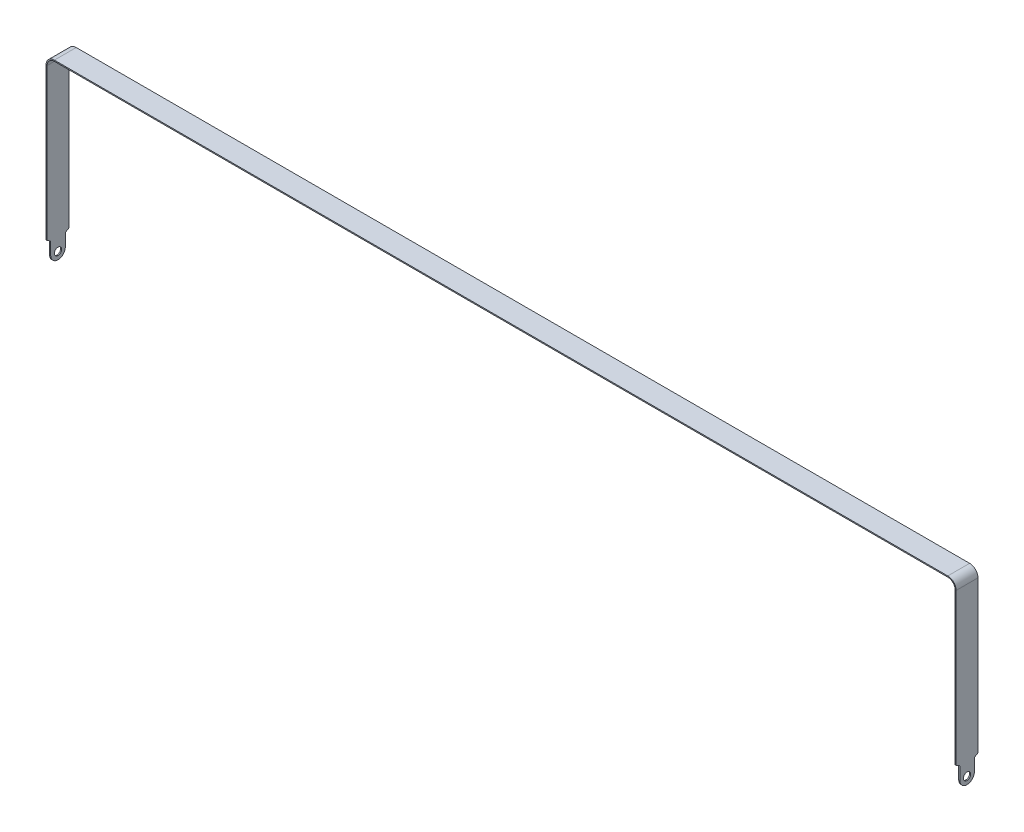
SolidWorks part; units mm, degrees
note: The reader was unsure of these and kept them because the rebuilt part matched: flange length of "Edge-Flange1".
ref_plane "Front Plane" through (0, 0, 0) normal (0, 0, 1) x (1, 0, 0)
ref_plane "Top Plane" through (0, 0, 0) normal (0, 1, 0) x (1, 0, 0)
ref_plane "Right Plane" through (0, 0, 0) normal (1, 0, 0) x (0, 0, -1)
sketch "Sketch1" plane through (0, 0, 0) normal (0, 1, 0) x (1, 0, 0)
  line L3 (-311.75, -7.5) -> (311.75, -7.5)
  line L4 (-311.75, -7.5) -> (-311.75, 7.5)
  line L5 (-311.75, 7.5) -> (311.75, 7.5)
  line L6 (311.75, -7.5) -> (311.75, 7.5)
  line L7 (-311.75, -7.5) -> (311.75, 7.5) construction
  line L8 (-311.75, 7.5) -> (311.75, -7.5) construction
  point P0 (0, 0)
  dimension "D1" = 623.5
  dimension "D2" = 15
base flange "Base-Flange2" sketch "Sketch1" thickness 0.75 reverse thickness direction no parameters "D1"=0.7366
edge flange "Edge-Flange1" sketch "Sketch15" flange profiles "Sketch15", "Sketch16" flange angle 90 flange length 125 flange position material outside bend radius 5 thickness 0.75 relief rectangular parameters "D6"=10, "D8"=0.25
sketch "Sketch15" plane through (311.75, -0.75, 0) normal (-1, 0, 0) x (0, 0, -1)
  line L2 (-7.5, 0) -> (-7.5, 124.25)
  line L3 (-7.5, 124.25) -> (7.5, 124.25)
  line L4 (7.5, 124.25) -> (7.5, 0)
  line L5 (7.5, 0) -> (-7.5, 0) construction
  line L6 (7.5, 0) -> (-7.5, 0)
sketch "Sketch16" plane through (-311.75, -0.75, 0) normal (1, 0, 0) x (0, 0, 1)
  line L0 (7.5, 0) -> (-7.5, 0) construction
  line L1 (7.5, 0) -> (-7.5, 0)
  line L2 (7.5, 0) -> (7.5, 124.25)
  line L3 (7.5, 124.25) -> (-7.5, 124.25)
  line L4 (-7.5, 124.25) -> (-7.5, 0)
bend "EdgeBend1" bend radius 5 bend angle 90 parameters "D5"=1
bend "EdgeBend2" bend radius 5 bend angle 90 parameters "D5"=2
sketch "Sketch17" plane through (312.5, 0, 0) normal (1, 0, 0) x (0, 0, -1)
  line L0 (0, -125) -> (0, -95.6548) construction
  line L1 (7.5, -125) -> (-7.5, -125) construction
  line L4 (-5, -111.2863) -> (-5, -120)
  line L5 (5, -120) -> (5, -111.2863)
  line L6 (5, -111.2863) -> (9.9611, -108.3867)
  line L7 (9.9611, -108.3867) -> (9.9611, -134.1714)
  line L8 (9.9611, -134.1714) -> (-9.9611, -134.1714)
  line L9 (-9.9611, -108.3867) -> (-9.9611, -134.1714)
  line L10 (-5, -111.2863) -> (-9.9611, -108.3867)
  circle A0 centre (0, -120) radius 2.5
  arc A1 (-5, -120) -> (5, -120) centre (0, -120) ccw
  point P14 (0, -134.1714)
  dimension "D2" = 5
  dimension "D1" = 5
  dimension "D3" = 10
extrude "Cut-Extrude1" cut sketch "Sketch17" against normal through all normal cut yes
sketch "Bend-Lines3" [suppressed] plane through (0, 0, 0) normal (0, 1, 0) x (1, 0, 0)
sketch "Bounding-Box3" [suppressed] plane through (0, 0, 0) normal (0, 1, 0) x (1, 0, 0)
sheet metal parameters "Sheet-Metal2" thickness 0.75 parameters "D1"=0.7366
flat pattern "Flat-Pattern2" [suppressed]
sketch "Bend-Lines4" plane through (0, 0, 0) normal (0, 1, 0) x (1, 0, 0)
sketch3d "Bounding-Box4" [suppressed]
  line L0 (-311.75, 6, 0) -> (311.75, 6, 0) construction
  line L1 (-311.75, -6, 0) -> (311.75, -6, 0) construction
  line L2 (-311.75, 6, 0) -> (-311.75, -6, 0) construction
  line L3 (311.75, 6, 0) -> (311.75, -6, 0) construction
sheet metal parameters "Sheet-Metal3" thickness 0.75 parameters "D1"=0.7366
flat pattern "Flat-Pattern2"
sketch "Bend-Lines4" plane through (0, 0, 0) normal (0, 1, 0) x (1, 0, 0)
  line L0 (-310.9715, 6) -> (-310.9715, -6) construction
  line L1 (310.9715, -6) -> (310.9715, 6) construction
  line L2 (-310.9715, 6) -> (-310.9715, -6) construction
  line L3 (310.9715, -6) -> (310.9715, 6) construction
sketch3d "Bounding-Box4" [suppressed]
  line L0 (434.443, 6, 0) -> (-434.443, 6, 0) construction
  line L1 (434.443, -6, 0) -> (-434.443, -6, 0) construction
  line L2 (434.443, 6, 0) -> (434.443, -6, 0) construction
  line L3 (-434.443, 6, 0) -> (-434.443, -6, 0) construction
bend of the flat pattern "Flatten-<EdgeBend1>1"
bend of the flat pattern "Flatten-<EdgeBend2>1"
sheet metal parameters "Sheet-Metal4" thickness 0.75 parameters "D1"=0.7366
flat pattern "Flat-Pattern2"
sketch "Bend-Lines4" plane through (0, 0, 0) normal (0, 1, 0) x (1, 0, 0)
  line L0 (-310.9715, 7.5) -> (-310.9715, -7.5) construction
  line L1 (310.9715, -7.5) -> (310.9715, 7.5) construction
  line L2 (-310.9715, 7.5) -> (-310.9715, -7.5) construction
  line L3 (310.9715, -7.5) -> (310.9715, 7.5) construction
sketch3d "Bounding-Box4" [suppressed]
  line L0 (434.4428, 7.5, 0) -> (-434.4428, 7.5, 0) construction
  line L1 (434.4428, -7.5, 0) -> (-434.4428, -7.5, 0) construction
  line L2 (434.4428, 7.5, 0) -> (434.4428, -7.5, 0) construction
  line L3 (-434.4428, 7.5, 0) -> (-434.4428, -7.5, 0) construction
bend of the flat pattern "Flatten-<EdgeBend1>1"
bend of the flat pattern "Flatten-<EdgeBend2>1"
